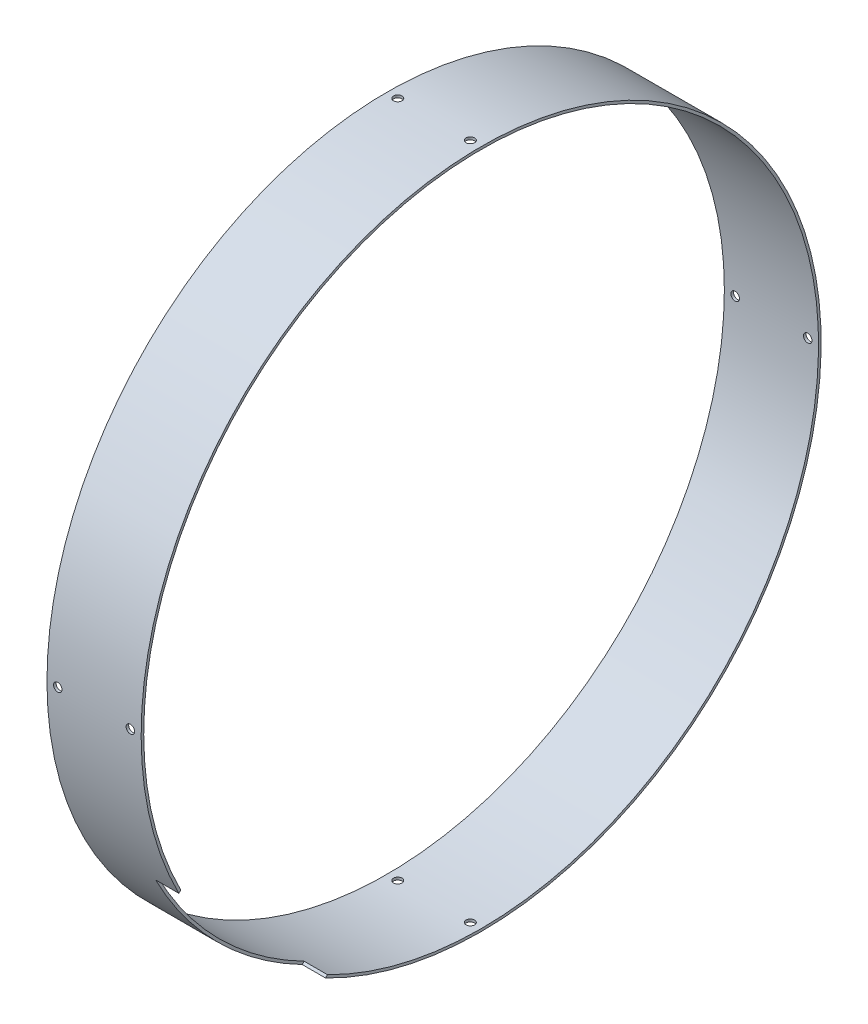
SolidWorks part; units mm, degrees
material "6061 Alloy"
ref_plane "Front Plane" through (0, 0, 0) normal (0, 0, 1) x (1, 0, 0)
ref_plane "Top Plane" through (0, 0, 0) normal (0, 1, 0) x (1, 0, 0)
ref_plane "Right Plane" through (0, 0, 0) normal (1, 0, 0) x (0, 0, -1)
sketch "Sketch1" plane through (0, 0, 0) normal (1, 0, 0) x (0, 0, -1)
  circle A0 centre (0, 0) radius 100
  circle A1 centre (0, 0) radius 99.238
  dimension "D1" = 200
  dimension "D2" = 0.762
extrude "Boss-Extrude1" add sketch "Sketch1" along normal blind 27.7
ref_plane "Plane1" through (0, 0, 100) normal (0, 0, 1) x (1, 0, 0)
hole_wizard "Ø2.5mm Dowel Hole1" positions "Sketch2" profile "Sketch3" hole size "Ø2.5" standard "ANSI Metric" end condition through all
sketch "Sketch2" plane through (0, 0, 100) normal (0, 0, 1) x (1, 0, 0)
  line L0 (27.7, -100) -> (27.7, 100) construction
  line L1 (0, 100) -> (0, -100) construction
  point P0 (24.525, 0)
  point P2 (3.175, 0)
  dimension "D1" = 3.175
  dimension "D2" = 3.175
sketch "Sketch3" plane through (24.525, 0, 100) normal (1, 0, 0) x (0, -1, 0)
  line L0 (0, 0) -> (0, 200)
  line L1 (0, 200) -> (1.25, 200)
  line L2 (1.25, 200) -> (1.25, 0)
  line L5 (1.25, 0) -> (0, 0)
  line L11 (0, -6.35) -> (0, 107.95) construction
  dimension "Thru Hole Dia." = 2.5
  dimension "Thru Hole Depth" = 200
ref_plane "Plane2" through (0, 100, 0) normal (0, 1, 0) x (1, 0, 0)
hole_wizard "Ø2.5mm Dowel Hole2" positions "Sketch4" profile "Sketch5" hole size "Ø2.5" standard "ANSI Metric" end condition through all
sketch "Sketch4" plane through (0, 100, 0) normal (0, 1, 0) x (1, 0, 0)
  line L0 (27.7, -100) -> (27.7, 100) construction
  line L1 (0, 100) -> (0, -100) construction
  point P0 (24.525, 0)
  point P2 (3.175, 0)
  dimension "D1" = 3.175
  dimension "D2" = 3.175
sketch "Sketch5" plane through (24.525, 100, 0) normal (1, 0, 0) x (0, 0, 1)
  line L0 (0, 0) -> (0, 200)
  line L1 (0, 200) -> (1.25, 200)
  line L2 (1.25, 200) -> (1.25, 0)
  line L5 (1.25, 0) -> (0, 0)
  line L11 (0, -6.35) -> (0, 107.95) construction
  dimension "Thru Hole Dia." = 2.5
  dimension "Thru Hole Depth" = 200
ref_plane "Plane3" through (0, 0, 0) normal (0, 0.7071, -0.7071) x (-1, 0, 0)
sketch "Sketch6" plane through (0, 0, 0) normal (0, 0.7071, -0.7071) x (-1, 0, 0)
  line L0 (-21.35, 30) -> (-21.35, -30) construction
  line L1 (-21.35, 30) -> (-27.7, 30) construction
  line L2 (-21.35, -30) -> (-27.7, -30) construction
  line L3 (-27.7, 30) -> (-27.7, -30) construction
  line L5 (-27.7, 100) -> (-27.7, -100) construction
  line L6 (-20.85, 30.5) -> (-28.2, 30.5)
  line L7 (-28.2, 30.5) -> (-28.2, -30.5)
  line L8 (-20.85, -30.5) -> (-28.2, -30.5)
  line L9 (-20.85, 30.5) -> (-20.85, -30.5)
  point P9 (-27.7, 0)
  dimension "D1" = 60
  dimension "D2" = 6.35
  dimension "D3" = 0.5
extrude "Cut-Extrude1" cut sketch "Sketch6" against normal through all
ref_plane "Plane4" through (0, 0, 0) normal (0, 0.7071, 0.7071) x (-1, 0, 0)
sketch "Sketch7" plane through (0, 0, 0) normal (0, 0.7071, 0.7071) x (-1, 0, 0)
  line L0 (-27.7, 7.5) -> (-27.7, -7.5) construction
  line L1 (-27.7, 7.5) -> (-21.35, 7.5) construction
  line L2 (-27.7, -7.5) -> (-21.35, -7.5) construction
  line L3 (-21.35, 7.5) -> (-21.35, -7.5) construction
  line L4 (-27.7, 95.2352) -> (-27.7, -100) construction
  line L5 (-28.2, 8) -> (-20.85, 8)
  line L6 (-20.85, 8) -> (-20.85, -8)
  line L7 (-28.2, -8) -> (-20.85, -8)
  line L8 (-28.2, 8) -> (-28.2, -8)
  point P6 (-21.35, 0)
  dimension "D1" = 6.35
  dimension "D2" = 15
  dimension "D3" = 0.5
extrude "Cut-Extrude2" [suppressed] cut sketch "Sketch7" against normal through all both and the other way through all
